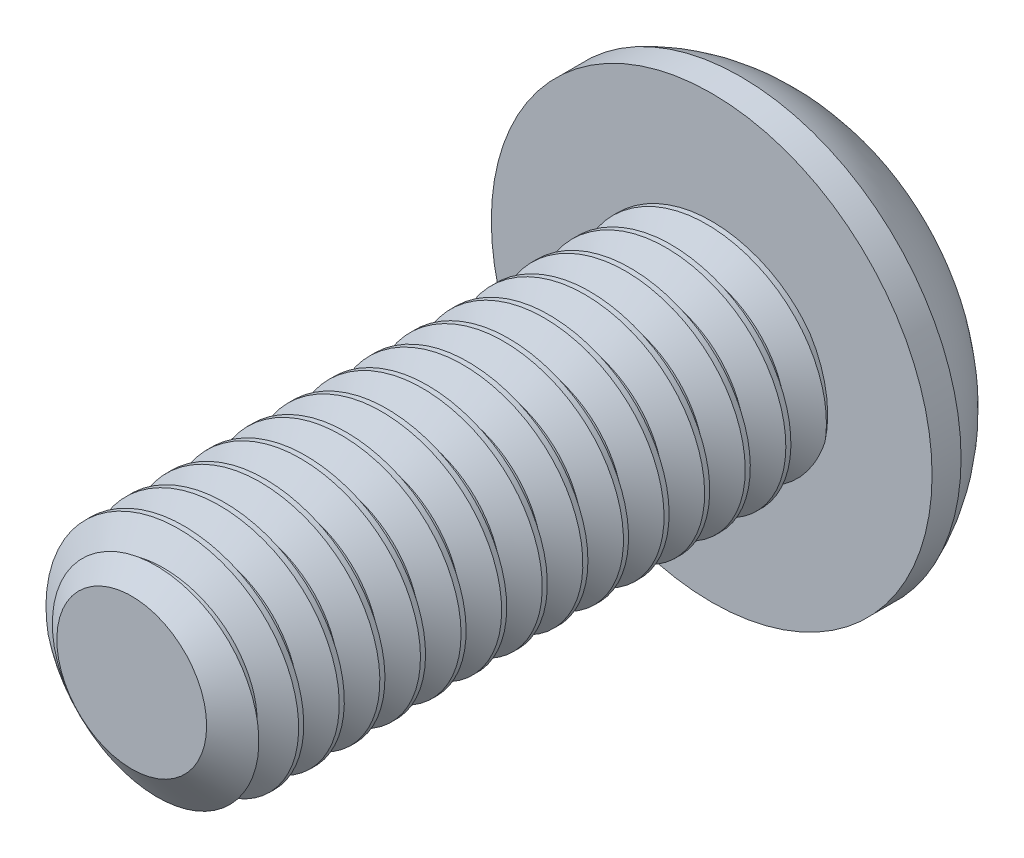
SolidWorks part; units mm, degrees
ref_plane "Front Plane" through (0, 0, 0) normal (0, 0, 1) x (1, 0, 0)
ref_plane "Top Plane" through (0, 0, 0) normal (0, 1, 0) x (1, 0, 0)
ref_plane "Right Plane" through (0, 0, 0) normal (1, 0, 0) x (0, 0, -1)
sketch "Sketch1" plane through (0, 0, 0) normal (0, 0, 1) x (1, 0, 0)
  circle A0 centre (0, 0) radius 2
  dimension "OD" = 4
extrude "Extrude1" add sketch "Sketch1" against normal blind 10
sketch "Sketch2" plane through (0, 0, 0) normal (0, 0, 1) x (1, 0, 0)
  circle A0 centre (0, 0) radius 2 construction
  circle A1 centre (0, 0) radius 2
curve "Helix/Spiral1" pitch 0.7 height 10.7 radius 2 centre (0, 0, 0) axis (0, 0, -1) start towards (0, 1, 0) parameters "pitch"=0.7
sketch "Sketch3" plane through (0, 0, 0) normal (1, 0, 0) x (0, 0, -1)
  line L0 (-0.6125, 2) -> (-0.35, 1.5453)
  line L1 (-0.35, 1.5453) -> (-0.2625, 1.5453)
  line L2 (-0.2625, 1.5453) -> (0, 2)
  line L3 (-0.6125, 2) -> (0, 2)
  line L4 (-0.3062, 2) -> (-0.3062, 1.5453) construction
  line L5 (-0.4812, 1.7727) -> (-0.1312, 1.7727) construction
  line L6 (0, 2) -> (0, -2) construction
  dimension "D1" = 0.0875
  dimension "D2" = 0.35
  dimension "D3" = 60
sweep "Cut-Sweep1" cut profiles "Sketch3" path "Helix/Spiral1"
sketch "Sketch4" plane through (0, 0, 0) normal (1, 0, 0) x (0, 0, -1)
  line L0 (0.4962, 2) -> (0, 1.2913)
  line L1 (0, 1.2913) -> (0, 2)
  line L2 (0.4962, 2) -> (0, 2)
  line L3 (-0.6125, 2) -> (0, 2) construction
  line L4 (0, 0) -> (7.0209, 0) construction
  dimension "D1" = 55
  dimension "D2" = 0.254
revolve "Cut-Revolve1" cut sketch "Sketch4" angle 360 about L4
sketch "Sketch5" plane through (0, 0, 0) normal (1, 0, 0) x (0, 0, -1)
  line L0 (10, 0.3311) -> (10, 1.814) construction
  line L1 (10, 2.127) -> (28.1202, 2.127)
  line L2 (10, 2.127) -> (10, 0)
  line L3 (10, 0) -> (28, 0)
  line L4 (28, 1.7968) -> (28, 0)
  line L5 (28.1202, 2.127) -> (28, 1.7968)
  line L6 (0, 0) -> (9.9695, 0) construction
  point P3 (28, 2.127)
  point P10 (28, 2.127)
  dimension "D1" = 0.3302
  dimension "Thread min" = 28
  dimension "D2" = 0.127
  dimension "D3" = 20
revolve "partially thread" [suppressed] add sketch "Sketch5" angle 360 about L6
sketch "Sketch6" plane through (0, 0, -10) normal (0, 0, -1) x (-1, 0, 0)
  circle A0 centre (0, 0) radius 3.8
  dimension "head dia" = 7.6
extrude "Extrude2" add sketch "Sketch6" along normal blind 2.2
sketch "Sketch10" plane through (0, 0, 0) normal (1, 0, 0) x (0, 0, -1)
  line L0 (12.2, -3.8) -> (12.2, 3.8) construction
  line L1 (0, 0) -> (15.9584, 0) construction
  line L2 (12.2, 3.8) -> (10, 3.8) construction
  line L3 (10, 3.8) -> (10, -3.8) construction
  line L4 (10.5, 3.8) -> (10.5, 4.3)
  line L5 (10.5, 4.3) -> (12.7, 4.3)
  line L6 (12.7, 4.3) -> (12.7, 1.25)
  line L7 (12.2, 1.25) -> (12.7, 1.25)
  arc A0 (12.2, 1.25) -> (10.5, 3.8) centre (9.4375, 1.25) ccw
  dimension "D1" = 2.5
  dimension "D2" = 0.5
  dimension "D3" = 0.5
revolve "Cut-Revolve2" cut sketch "Sketch10" angle 360 about L1
ref_plane "Plane1" through (0, 0, -12.2) normal (0, 0, 1) x (1, 0, 0)
sketch "Sketch7" plane through (0, 0, -12.2) normal (0, 0, -1) x (-1, 0, 0)
  line L1 (0, 1.4434) -> (-1.25, 0.7217)
  line L2 (-1.25, 0.7217) -> (-1.25, -0.7217)
  line L3 (-1.25, -0.7217) -> (0, -1.4434)
  line L4 (0, -1.4434) -> (1.25, -0.7217)
  line L5 (1.25, -0.7217) -> (1.25, 0.7217)
  line L6 (1.25, 0.7217) -> (0, 1.4434)
  circle A0 centre (0, 0) radius 1.25 construction
  dimension "hex dia" = 2.5
extrude "Cut-Extrude1" cut sketch "Sketch7" against normal blind 1.875
sketch "Sketch8" plane through (0, 0, -12.2) normal (0, 0, 1) x (1, 0, 0)
  circle A0 centre (0, 0) radius 1.4434
extrude "Cut-Extrude2" cut sketch "Sketch8" along normal through all draft 45
sketch "Sketch9" plane through (0, 0, 0) normal (1, 0, 0) x (0, 0, -1)
  line L0 (0, 2) -> (0, -2) construction
  line L1 (3.85, 2) -> (3.85, -2) construction
  dimension "D1" = 3.85
equation "\"D3@Helix/Spiral1\" = \"screw length@Extrude1\"+\"pitch@Helix/Spiral1\""
equation "\"D1@Sketch3\" = \"pitch@Helix/Spiral1\"*.125"
equation "\"D2@Sketch3\" = \"pitch@Helix/Spiral1\"*.5"
equation "\"D1@Cut-Extrude1\" = \"hex dia@Sketch7\"*.75"
equation "\"D1@Sketch9\" = \"pitch@Helix/Spiral1\"*5.5"
equation "\"D1@Sketch10\" = \"hex dia@Sketch7\""
equation "\"D1@Plane1\" = \"head depth@Extrude2\""
